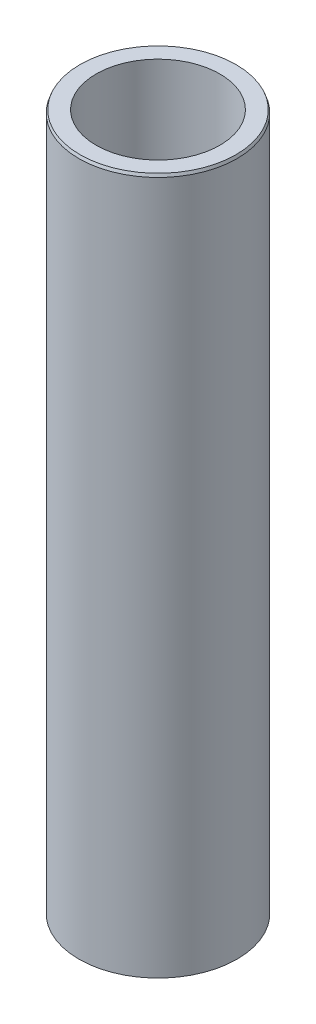
SolidWorks part; units mm, degrees
ref_plane "Front Plane" through (0, 0, 0) normal (0, 0, 1) x (1, 0, 0)
ref_plane "Top Plane" through (0, 0, 0) normal (0, 1, 0) x (1, 0, 0)
ref_plane "Right Plane" through (0, 0, 0) normal (1, 0, 0) x (0, 0, -1)
sketch "Sketch1" plane through (0, 0, 0) normal (0, 1, 0) x (1, 0, 0)
  circle A0 centre (0, 0) radius 55
  dimension "SHAFT_OD" = 110
extrude "Boss-Extrude1" add sketch "Sketch1" along normal blind 484.7851
sketch "Sketch2" plane through (0, 0, 0) normal (0, 1, 0) x (1, 0, 0)
  circle A0 centre (0, 0) radius 43.0017
  dimension "BORE_D" = 86.0035
extrude "Cut-Extrude1" cut sketch "Sketch2" along normal through all
chamfer "Chamfer1" distance 2.0032 angle 20.323 2 edges at (0, 484.7851, 55) (0, 0, 55) first distance on face at (0, 484.7851, 55) first distance on face at (0, 0, 43.0017)
